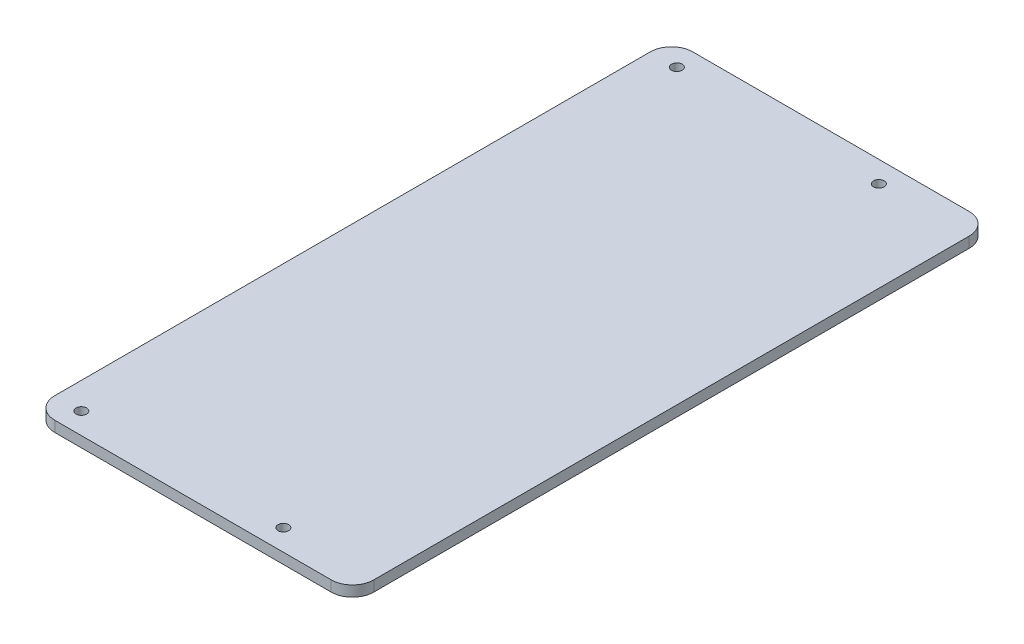
SolidWorks part; units mm, degrees
ref_plane "Front Plane" through (0, 0, 0) normal (0, 0, 1) x (1, 0, 0)
ref_plane "Top Plane" through (0, 0, 0) normal (0, 1, 0) x (1, 0, 0)
ref_plane "Right Plane" through (0, 0, 0) normal (1, 0, 0) x (0, 0, -1)
sketch "Sketch1" plane through (0, 0, 0) normal (0, 1, 0) x (1, 0, 0)
  line L0 (-37.5, 84) -> (-37.5, -84) construction
  line L1 (-39, -90) -> (39, -90)
  line L2 (-45, -84) -> (-45, 84)
  line L3 (-39, 90) -> (39, 90)
  line L4 (45, -84) -> (45, 84)
  line L5 (-45, -90) -> (45, 90) construction
  line L6 (-45, 90) -> (45, -90) construction
  line L7 (-37.5, -84) -> (19.5, -84) construction
  line L8 (19.5, -84) -> (19.5, 84) construction
  line L9 (19.5, 84) -> (-37.5, 84) construction
  arc A0 (39, 90) -> (45, 84) centre (39, 84) cw
  arc A1 (45, -84) -> (39, -90) centre (39, -84) cw
  arc A2 (-39, -90) -> (-45, -84) centre (-39, -84) cw
  arc A3 (-45, 84) -> (-39, 90) centre (-39, 84) cw
  circle A4 centre (19.5, -84) radius 1.5
  circle A5 centre (-37.5, -84) radius 1.5
  circle A6 centre (19.5, 84) radius 1.5
  circle A7 centre (-37.5, 84) radius 1.5
  point P0 (0, 0)
  dimension "D3" = 3
  dimension "D4" = 6
  dimension "D5" = 7.5
  dimension "D6" = 57
  dimension "D7" = 168
  dimension "D8" = 6
  dimension "D1" = 90
  dimension "D2" = 180
extrude "Boss-Extrude1" add sketch "Sketch1" along normal blind 3
